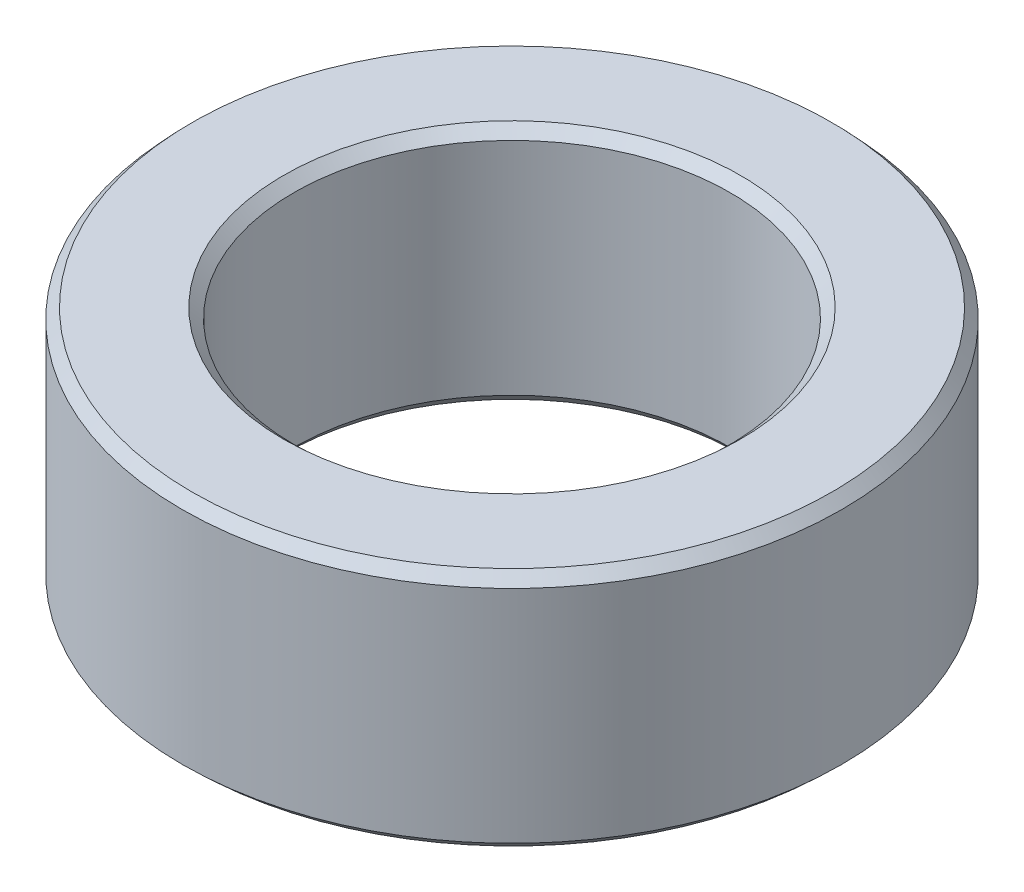
SolidWorks part; units mm, degrees
ref_plane "Front Plane" through (0, 0, 0) normal (0, 0, 1) x (1, 0, 0)
ref_plane "Top Plane" through (0, 0, 0) normal (0, 1, 0) x (1, 0, 0)
ref_plane "Right Plane" through (0, 0, 0) normal (1, 0, 0) x (0, 0, -1)
sketch "Sketch1" plane through (0, 0, 0) normal (0, 1, 0) x (1, 0, 0)
  circle A0 centre (0, 0) radius 55
  dimension "SLEEVE_OD" = 110
extrude "Boss-Extrude1" add sketch "Sketch1" along normal blind 40.1695
sketch "Sketch2" plane through (0, 0, 0) normal (0, 1, 0) x (1, 0, 0)
  circle A0 centre (0, 0) radius 36.3898
  dimension "BORE_D" = 72.7796
extrude "Cut-Extrude1" cut sketch "Sketch2" along normal through all
chamfer "Chamfer1" distance 1.733 angle 43.015 4 edges at (0, 40.1695, 36.3898) (0, 0, 36.3898) (0, 0, 55) (0, 40.1695, 55) first distance on face at (0, 40.1695, 36.3898) first distance on face at (0, 0, 36.3898) first distance on face at (0, 40.1695, 55)
